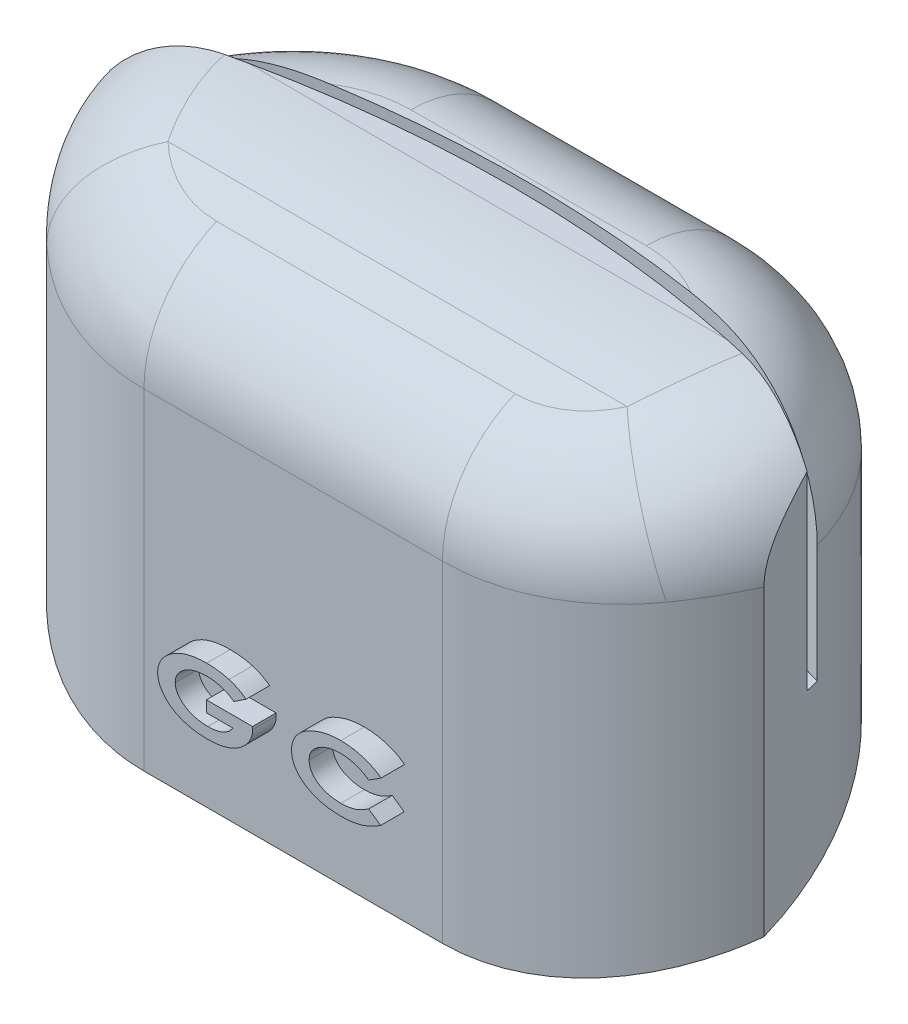
SolidWorks part; units mm, degrees
ref_plane "Front Plane" through (0, 0, 0) normal (0, 0, 1) x (1, 0, 0)
ref_plane "Top Plane" through (0, 0, 0) normal (0, 1, 0) x (1, 0, 0)
ref_plane "Right Plane" through (0, 0, 0) normal (1, 0, 0) x (0, 0, -1)
sketch "Sketch1" plane through (0, 0, 0) normal (0, 1, 0) x (1, 0, 0)
  line L1 (-30, -15) -> (30, -15)
  line L2 (-30, -15) -> (-30, 15)
  line L3 (-30, 15) -> (30, 15)
  line L4 (30, -15) -> (30, 15)
  line L5 (-30, -15) -> (30, 15) construction
  line L6 (-30, 15) -> (30, -15) construction
  point P0 (0, 0)
  dimension "D1" = 30
  dimension "D2" = 60
extrude "Boss-Extrude1" add sketch "Sketch1" along normal blind 40
sketch "Sketch2" plane through (0, 40, 0) normal (0, 1, 0) x (1, 0, 0)
  line L0 (-30, 15) -> (-30, -15) construction
  line L1 (30, -15) -> (30, 15) construction
  line L2 (-29.6972, -0.9531) -> (-30, -2.4607)
  line L3 (-30, -2.4607) -> (-30, 0)
  line L4 (30, 0) -> (30, -2.4607)
  line L5 (30, -2.4607) -> (29.6972, -0.9531)
  arc A0 (-30, 0) -> (30, 0) centre (0, -94.4208) cw
  arc A1 (-29.6972, -0.9531) -> (29.6972, -0.9531) centre (0, -94.4208) cw
  dimension "D1" = 1
extrude "Cut-Extrude1" cut sketch "Sketch2" against normal blind 20
sketch "Sketch3" plane through (-30, 0, 0) normal (-1, 0, 0) x (0, 0, 1)
  line L0 (15, 0) -> (-15, 12.4264)
  line L1 (-15, 40) -> (-15, 0) construction
  line L2 (-15, 12.4264) -> (-15, 0)
  line L3 (-15, 0) -> (15, 0)
  dimension "D1" = 22.5
extrude "Cut-Extrude2" cut sketch "Sketch3" against normal through all
sketch "Sketch5" plane through (-30, 0, 0) normal (-1, 0, 0) x (0, 0, 1)
  line L0 (2.4607, 40) -> (15, 34.8061)
  line L1 (15, 40) -> (15, 0) construction
  line L2 (15, 34.8061) -> (15, 40)
  line L3 (15, 40) -> (2.4607, 40)
  dimension "D1" = 22.5
extrude "Cut-Extrude3" cut sketch "Sketch5" against normal through all
fillet "Fillet2" radius 20 1 edges at (0, 40, 2.4607)
fillet "Fillet3" radius 20 2 edges at (30, 26.2132, -15) (-30, 26.2132, -15)
fillet "Fillet4" radius 20 2 edges at (30, 17.403, 15) (-30, 17.403, 15)
fillet "Fillet5" radius 10 5 edges at (22.0943, 35.7814, 12.6454) (-22.0943, 35.7814, 12.6454) (0, 34.8061, 15)
sketch "Sketch6" plane through (0, 0, 15) normal (0, 0, 1) x (1, 0, 0)
  text T0 "GC" font "Century Gothic" height in points 20
extrude "Boss-Extrude2" add sketch "Sketch6" along normal blind 2
fillet "Fillet6" radius 10 3 edges at (22.1584, 40, -10.8799) (0, 40, -15) (-22.1584, 40, -10.8799)
